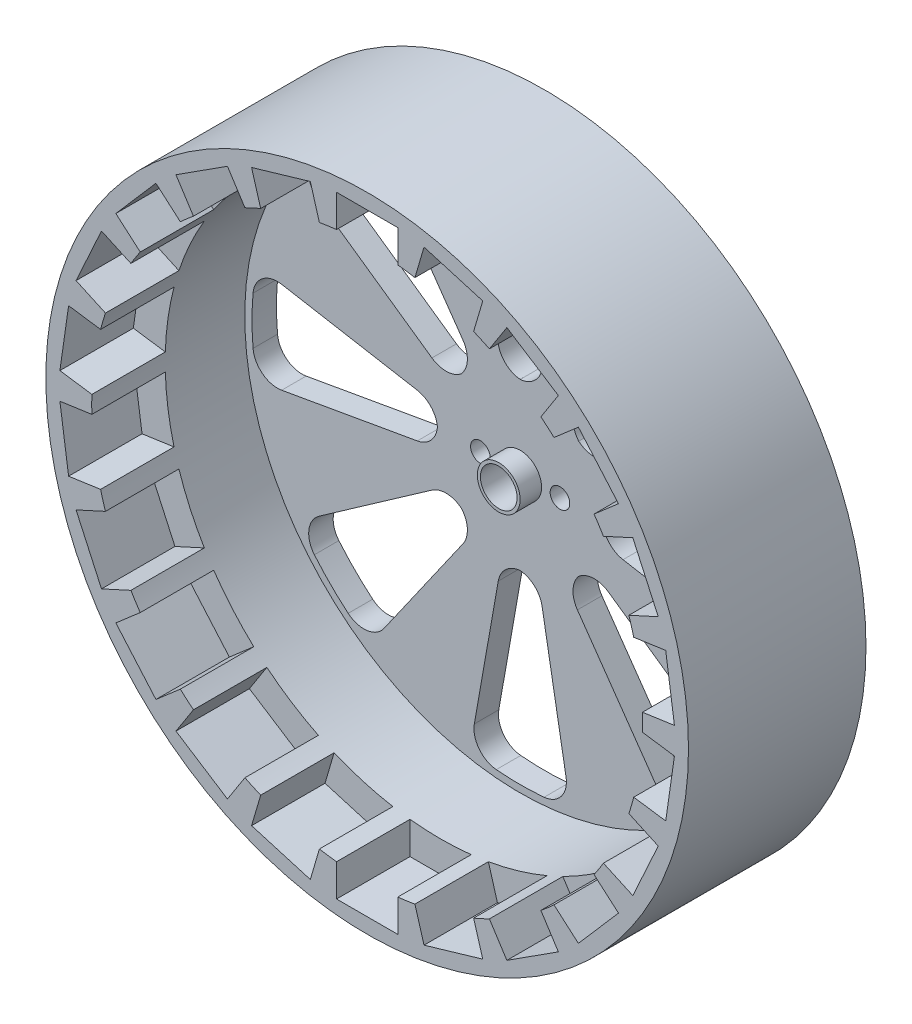
SolidWorks part; units mm, degrees
ref_plane "正面" through (0, 0, 0) normal (0, 0, 1) x (1, 0, 0)
ref_plane "平面" through (0, 0, 0) normal (0, 1, 0) x (1, 0, 0)
ref_plane "右側面" through (0, 0, 0) normal (1, 0, 0) x (0, 0, -1)
sketch "ｽｹｯﾁ1" plane through (0, 0, 0) normal (0, 0, 1) x (1, 0, 0)
  circle A0 centre (0, 0) radius 45
  circle A1 centre (0, 0) radius 52.5
  dimension "D1" = 90
  dimension "D2" = 105
extrude "ﾎﾞｽ - 押し出し1" add sketch "ｽｹｯﾁ1" along normal blind 25
extrude "ﾎﾞｽ - 押し出し2" add sketch "ｽｹｯﾁ1<2>" against normal blind 4 contours A1
sketch "ｽｹｯﾁ1<2>" plane through (0, 0, 0) normal (0, 0, 1) x (1, 0, 0) same geometry as "ｽｹｯﾁ1"
sketch "ｽｹｯﾁ2" plane through (0, 0, -4) normal (0, 0, -1) x (-1, 0, 0)
  line L0 (-6.5, 0) -> (6.5, 0)
  circle A0 centre (0, 0) radius 3
  circle A1 centre (6.5, 0) radius 1.6
  circle A2 centre (-6.5, 0) radius 1.6
  point P6 (0, 0)
  dimension "D1" = 6
  dimension "D3" = 3.2
  dimension "D4" = 3.2
  dimension "D2" = 6.5
extrude "ｶｯﾄ - 押し出し1" cut sketch "ｽｹｯﾁ2" against normal blind 4 contours A2 | A0 | A1
sketch "ｽｹｯﾁ3" plane through (0, 0, 0) normal (0, 0, 1) x (1, 0, 0)
  circle A0 centre (0, 0) radius 3
  circle A1 centre (0, 0) radius 3.5
  dimension "D1" = 6
  dimension "D2" = 7
extrude "ﾎﾞｽ - 押し出し3" add sketch "ｽｹｯﾁ3" along normal blind 3.5
sketch "ｽｹｯﾁ4" plane through (0, 0, -4) normal (0, 0, -1) x (-1, 0, 0)
  line L0 (0, -10) -> (0, -13.5)
  line L1 (0, -13.5) -> (-3, -13.5)
  line L2 (-3, -13.5) -> (-8.2094, -43.0442)
  line L3 (0, -13.5) -> (3, -13.5)
  line L4 (3, -13.5) -> (8.2094, -43.0442)
  circle A0 centre (0, 0) radius 10
  arc A1 (-8.2094, -43.0442) -> (8.2094, -43.0442) centre (0, 0) ccw
  dimension "D1" = 20
  dimension "D2" = 3.5
  dimension "D3" = 3
  dimension "D4" = 100
  dimension "D5" = 3
  dimension "D6" = 30
  dimension "D7" = 100
extrude "ｶｯﾄ - 押し出し3" cut sketch "ｽｹｯﾁ4" against normal blind 15 contours L1 L2 A1 L4 L3
fillet "ﾌｨﾚｯﾄ2" radius 4 4 edges at (3, -13.5, -2) (-3, -13.5, -2) (-8.2094, -43.0442, -2) (8.2094, -43.0442, -2)
pattern_circular "円形ﾊﾟﾀｰﾝ1" count 8 over 360 about axis through (0, 0, -4) along (0, 0, 1) of "ﾌｨﾚｯﾄ2", "ｶｯﾄ - 押し出し3"
sketch "ｽｹｯﾁ5" plane through (0, 0, 25) normal (0, 0, 1) x (1, 0, 0)
  line L0 (0, 0) -> (0, 45)
  line L1 (0, 45) -> (5, 45)
  line L2 (0, 45) -> (0, 52.5)
  line L3 (0, 45) -> (0, 50)
  line L5 (-5, 40) -> (5, 40)
  line L6 (-5, 40) -> (-5, 50)
  line L7 (-5, 50) -> (5, 50)
  line L8 (5, 40) -> (5, 50)
  line L9 (0, 50) -> (0, 40) construction
  line L10 (-5, 45) -> (5, 45) construction
  circle A0 centre (0, 0) radius 45 construction
  circle A2 centre (0, 0) radius 52.5 construction
  dimension "D1" = 5
  dimension "D2" = 7.5
  dimension "D3" = 5
extrude "ｶｯﾄ - 押し出し4" cut sketch "ｽｹｯﾁ5" against normal blind 12 contours L7 L8 L5 L6
pattern_circular "円形ﾊﾟﾀｰﾝ2" count 22 over 360 about axis through (0, 0, 25) along (0, 0, 1) of "ｶｯﾄ - 押し出し4"
